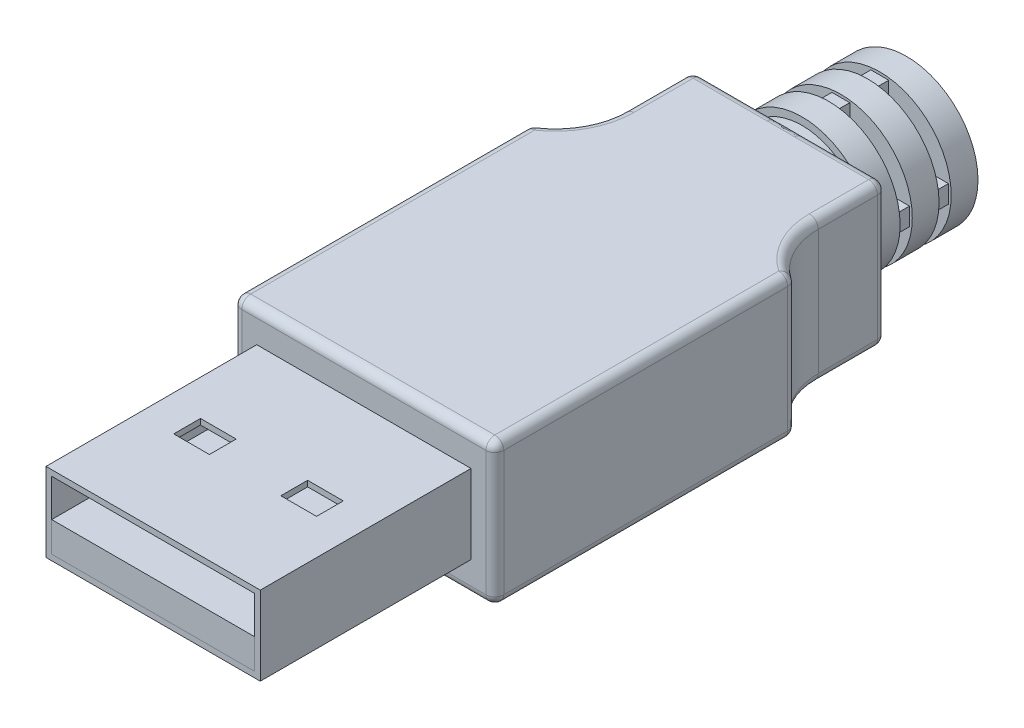
SolidWorks part; units mm, degrees
ref_plane "Front" through (0, 0, 0) normal (0, 0, 1) x (1, 0, 0)
ref_plane "Top" through (0, 0, 0) normal (0, 1, 0) x (1, 0, 0)
ref_plane "Right" through (0, 0, 0) normal (1, 0, 0) x (0, 0, -1)
sketch "Sketch1" plane through (0, 0, 0) normal (0, 0, 1) x (1, 0, 0)
  line L0 (-5.68, 1.89) -> (5.68, 1.89)
  line L1 (-6, 2.21) -> (6, 2.21)
  line L2 (-6, 2.21) -> (-6, -2.21)
  line L3 (-6, -2.21) -> (6, -2.21)
  line L4 (6, 2.21) -> (6, -2.21)
  line L5 (-6, 2.21) -> (6, -2.21) construction
  line L6 (-6, -2.21) -> (6, 2.21) construction
  line L7 (5.68, 1.89) -> (5.68, -1.89)
  line L8 (-5.68, -1.89) -> (5.68, -1.89)
  line L9 (-5.68, 1.89) -> (-5.68, -1.89)
  line L10 (-5.68, -0.21) -> (5.68, -0.21)
  point P0 (0, 0)
  dimension "D1" = 12
  dimension "D2" = 4.42
  dimension "D4" = 2
  dimension "D3" = 0.32
extrude "Boss-Extrude1" add sketch "Sketch1" against normal blind 11.8 contours L4 L1 L2 L3 L9 L0 L7 L8 | L10 L9 L8 L7 region at (0, -1.05, 0) region at (0, 2.0821, 0)
split line "Split Line1"
sketch "Sketch1<4>" plane through (0, 0, 0) normal (0, 0, 1) x (1, 0, 0) same geometry as "Sketch1"
sketch "Sketch4" plane through (0, 2.21, 0) normal (0, 1, 0) x (1, 0, 0)
  line L0 (-6, 0) -> (6, 0) construction
  line L1 (2, 5.15) -> (2, 6.65)
  line L2 (4, 6.65) -> (2, 6.65)
  line L3 (-6, 11.8) -> (0, 11.8) construction
  line L8 (-6, 11.8) -> (-6, 0) construction
  line L9 (-6, 0) -> (0, 0) construction
  line L10 (0, 11.8) -> (0, 0) construction
  line L11 (-6, 11.8) -> (0, 0) construction
  line L12 (-6, 0) -> (0, 11.8) construction
  line L13 (-6, 11.8) -> (-6, 0) construction
  line L15 (4, 5.15) -> (4, 6.65)
  line L16 (-4, 5.15) -> (-2, 5.15)
  line L17 (-4, 5.15) -> (-4, 6.65)
  line L18 (-4, 6.65) -> (-2, 6.65)
  line L19 (-2, 5.15) -> (-2, 6.65)
  line L20 (-4, 5.15) -> (-2, 6.65) construction
  line L21 (-4, 6.65) -> (-2, 5.15) construction
  line L22 (4, 5.15) -> (2, 5.15)
  line L23 (-6, 11.8) -> (6, 11.8) construction
  point P0 (-3, 5.9)
  point P11 (0, 9.3732)
  point P12 (0, 11.8)
  point P13 (-3, 5.9)
  dimension "D1" = 2
  dimension "D2" = 1.5
extrude "Cut-Extrude1" cut sketch "Sketch4" against normal up to next
sketch "Sketch5" plane through (0, 0, -11.8) normal (0, 0, -1) x (-1, 0, 0)
  line L1 (7.335, -4) -> (-7.335, -4)
  line L2 (7.335, -4) -> (7.335, 4)
  line L3 (7.335, 4) -> (-7.335, 4)
  line L4 (-7.335, -4) -> (-7.335, 4)
  line L5 (7.335, -4) -> (-7.335, 4) construction
  line L6 (7.335, 4) -> (-7.335, -4) construction
  point P0 (0, 0)
  dimension "D1" = 14.67
  dimension "D2" = 8
extrude "Boss-Extrude2" add sketch "Sketch5" along normal blind 23.85
sketch "Sketch6" plane through (0, 4, 0) normal (0, 1, 0) x (1, 0, 0)
  line L0 (0, 0) -> (0, 35.65) construction
  line L1 (-7.335, 35.65) -> (7.335, 35.65) construction
  line L2 (5.415, 35.65) -> (5.415, 31.83)
  line L3 (7.335, 35.65) -> (7.335, 11.8) construction
  line L4 (-5.415, 35.65) -> (-5.415, 31.83)
  arc A0 (5.415, 31.83) -> (7.335, 28.47) centre (9.315, 31.83) ccw
  arc A1 (-5.415, 31.83) -> (-7.335, 28.47) centre (-9.315, 31.83) cw
  point P11 (5.415, 31.5465)
  line M4 (7.335, 11.8) -> (7.335, 35.65)
  line M5 (7.335, 35.65) -> (-7.335, 35.65)
  line M6 (-7.335, 35.65) -> (-7.335, 11.8)
  dimension "D1" = 5.415
  dimension "D2" = 7.18
  dimension "D3" = 3.82
extrude "Cut-Extrude2" cut sketch "Sketch6" against normal through all contours L2 A0 M4 M5 | A1 L4 M5 M6 region at (6.4414, 4, -32.502) region at (-6.4414, 4, -32.502)
sketch "Sketch8" plane through (0, 0, -35.65) normal (0, 0, -1) x (-1, 0, 0)
  line L0 (-0.5, 3.8426) -> (-0.5, 1.833)
  line L1 (-1.833, 0.5) -> (-3.8426, 0.5)
  line L2 (-3.8426, 0.5) -> (-3.8426, 0)
  line L4 (-0.5, 3.8426) -> (0, 3.8426)
  line L5 (5.415, 4) -> (-5.415, 4) construction
  line L6 (0, 3.8426) -> (0, 1.9) construction
  line L7 (-1.9, 0) -> (-3.8426, 0) construction
  line L8 (0, 1.9) -> (0, 0) construction
  line L9 (0, 0) -> (-1.9, 0) construction
  line L10 (0.5, 1.833) -> (0.5, 3.8426)
  line L11 (3.8426, 0.5) -> (1.833, 0.5)
  line L12 (0.5, 3.8426) -> (0, 3.8426)
  line L13 (3.8426, 0.5) -> (3.8426, 0)
  line L14 (1.833, -0.5) -> (3.8426, -0.5)
  line L15 (0.5, -3.8426) -> (0.5, -1.833)
  line L16 (3.8426, -0.5) -> (3.8426, 0)
  line L17 (0.5, -3.8426) -> (0, -3.8426)
  line L18 (-0.5, -1.833) -> (-0.5, -3.8426)
  line L19 (-3.8426, -0.5) -> (-1.833, -0.5)
  line L20 (-0.5, -3.8426) -> (0, -3.8426)
  line L21 (-3.8426, -0.5) -> (-3.8426, 0)
  circle A0 centre (0, 0) radius 3.875 construction
  arc A2 (-0.5, 1.833) -> (-1.833, 0.5) centre (0, 0) ccw
  arc A3 (0, 1.9) -> (-0.5, 1.833) centre (0, 0) ccw construction
  arc A4 (-1.833, 0.5) -> (-1.9, 0) centre (0, 0) ccw construction
  arc A5 (1.833, 0.5) -> (0.5, 1.833) centre (0, 0) ccw
  arc A6 (0.5, -1.833) -> (1.833, -0.5) centre (0, 0) ccw
  arc A7 (-1.833, -0.5) -> (-0.5, -1.833) centre (0, 0) ccw
  point P14 (0, 4)
  point P15 (-3.875, 0)
  point P17 (0, 3.7973)
  dimension "D2" = 1.9
  dimension "D4" = 7.75
  dimension "D1" = 0.5
  dimension "D3" = 4
extrude "Boss-Extrude4" add sketch "Sketch8" along normal blind 5.5 from offset 1 contours L19 A7 L18 L20 L17 L15 A6 L14 L16 L13 L11 A5 L10 L12 L4 L0 A2 L1 L2 L21 region at (0, 0, -35.65)
sketch "Sketch9" plane through (0, 0, 0) normal (0, 1, 0) x (1, 0, 0)
  line L0 (0, 35.65) -> (0, 42.19)
  line L2 (0, 42.19) -> (4, 42.19)
  line L3 (4, 42.19) -> (4, 40.69)
  line L4 (4, 40.69) -> (0, 40.69)
  line L5 (0, 40.01) -> (4, 40.01)
  line L6 (4, 40.01) -> (4, 38.51)
  line L7 (4, 38.51) -> (0, 38.51)
  line L8 (0, 37.83) -> (4, 37.83)
  line L9 (4, 37.83) -> (4, 36.33)
  line L10 (4, 36.33) -> (3.585, 36.33)
  line L11 (3.585, 36.33) -> (3.585, 35.65)
  line L13 (4, 40.69) -> (4, 40.01) construction
  line L14 (4, 38.51) -> (4, 37.83) construction
  line L15 (3.585, 35.65) -> (0, 35.65)
  line L16 (3.585, 36.33) -> (0, 36.33) construction
  line L17 (-5.415, 35.65) -> (5.415, 35.65) construction
  point P2 (0, 36.277)
  point P14 (0, 0)
  point P18 (0, 0)
  dimension "D1" = 1.5
  dimension "D2" = 0.68
  dimension "D3" = 3.585
  dimension "D4" = 4
  dimension "D5" = 6.54
revolve "Revolve1" add sketch "Sketch9" angle 360 about L0 region at (2, 0, -41.44) region at (2, 0, -39.26) region at (1.9401, 0, -36.7651)
fillet "Fillet1" radius 0.5 22 edges at (-5.9289, -4, -29.8951) (5.9289, -4, -29.8951) (7.335, 4, -20.135) (0, 4, -11.8) (-7.335, 4, -20.135) (-5.9289, 4, -29.8951) (-5.415, 4, -33.74) (0, 4, -35.65) (5.415, 4, -33.74) (5.9289, 4, -29.8951) (0, -4, -35.65) (0, -4, -11.8) (-5.415, 0, -35.65) (5.415, 0, -35.65) (7.335, 0, -11.8) (7.335, 0, -28.47) (-7.335, 0, -28.47) (-7.335, 0, -11.8) (-7.335, -4, -20.135) (-5.415, -4, -33.74) (5.415, -4, -33.74) (7.335, -4, -20.135)
